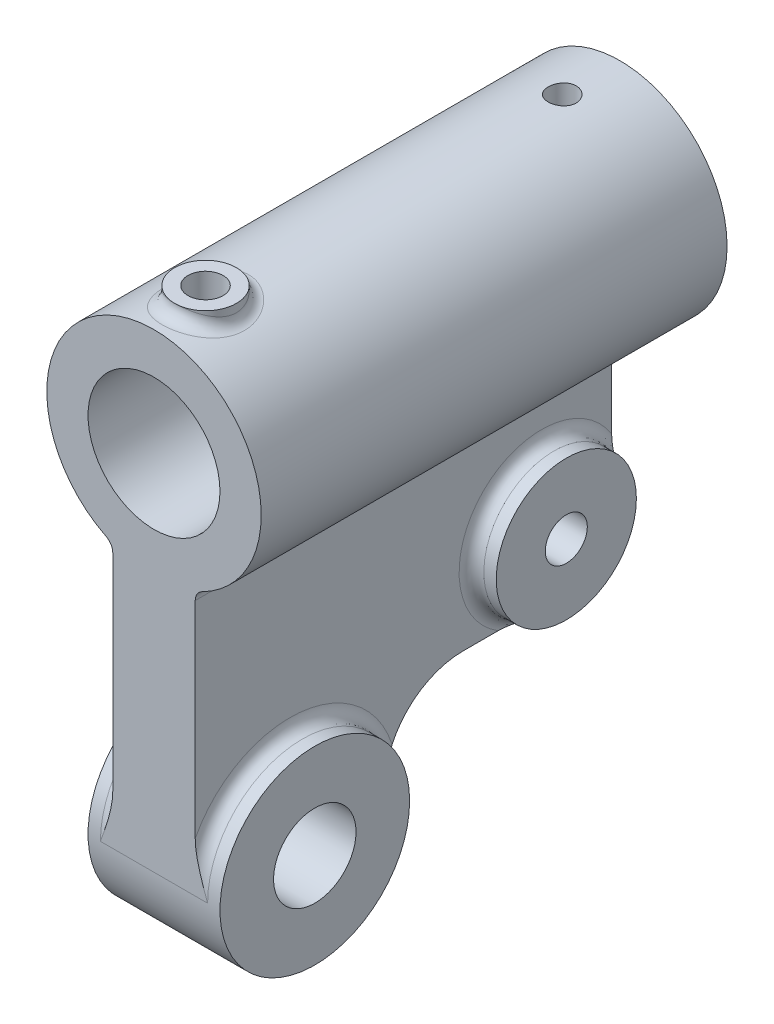
SolidWorks part; units mm, degrees
ref_plane "前基準面" through (0, 0, 0) normal (0, 0, 1) x (1, 0, 0)
ref_plane "上基準面" through (0, 0, 0) normal (0, 1, 0) x (1, 0, 0)
ref_plane "右基準面" through (0, 0, 0) normal (1, 0, 0) x (0, 0, -1)
sketch "草圖1" plane through (0, 0, 0) normal (0, 0, 1) x (1, 0, 0)
  circle A0 centre (0, 0) radius 26
  circle A1 centre (0, 0) radius 16
  dimension "D1" = 52
  dimension "D2" = 32
extrude "伸長1" add sketch "草圖1" against normal blind 113
sketch "草圖2" plane through (0, 0, 0) normal (1, 0, 0) x (0, 0, -1)
  line L0 (12.5, 12.9939) -> (12.5, 38.1989) construction
  line L1 (12.5, 29) -> (5, 29)
  line L2 (5, 29) -> (5, 21.929)
  line L3 (5, 21.929) -> (12.5, 21.929)
  line L4 (0, 26) -> (0, -26) construction
  line L5 (113, 26) -> (0, 26) construction
  line L6 (12.5, 29) -> (12.5, 21.929)
  dimension "D1" = 12.5
  dimension "D2" = 15
  dimension "D3" = 3
revolve "旋轉1" add sketch "草圖2" angle 360 about L0
sketch "草圖4" plane through (0, 0, 0) normal (1, 0, 0) x (0, 0, -1)
  line L0 (0, -16.5) -> (0, -88)
  line L1 (0, 26) -> (0, -26) construction
  line L2 (65, -69) -> (84, -69)
  line L3 (101, -52) -> (101, -16.5)
  line L7 (101, -16.5) -> (0, -16.5)
  line L8 (0, -16) -> (113, -16) construction
  arc A0 (0, -88) -> (46, -88) centre (23, -88) ccw
  arc A1 (46, -88) -> (65, -69) centre (65, -88) cw
  arc A2 (84, -69) -> (101, -52) centre (84, -52) ccw
  circle A4 centre (23, -88) radius 10
  dimension "D1" = 23
  dimension "D2" = 20
  dimension "D3" = 88
  dimension "D4" = 36
  dimension "D5" = 17
  dimension "D6" = 61
  dimension "D8" = 0.5
extrude "伸長2" add sketch "草圖4" along normal mid plane 20 contours L0 A0 A1 L2 A2 L3 A4 region at (0, -52.2468, -44.3643)
sketch "草圖5" plane through (0, 0, 0) normal (1, 0, 0) x (0, 0, -1)
  circle A0 centre (23, -88) radius 23
  arc A1 (0, -88) -> (46, -88) centre (23, -88) ccw construction
  circle A2 centre (23, -88) radius 10 construction
  circle A3 centre (23, -88) radius 10
extrude "伸長3" add sketch "草圖5" along normal mid plane 32
sketch "草圖6" plane through (10, 0, 0) normal (1, 0, 0) x (0, 0, -1)
  circle A0 centre (84, -52) radius 17
  arc A1 (84, -69) -> (101, -52) centre (84, -52) ccw construction
extrude "伸長4" add sketch "草圖6" along normal blind 6
fillet "圓角1" radius 3 1 edges at (0, -26, -101)
fillet "圓角2" radius 3 6 edges at (-1.3841, 25.9631, -5.1288) (-10, -65, -23) (10, -65, -23) (10, -39.9792, -71.9792) (-10, -24, -52) (10, -24, -52)
hole_wizard "M10 螺紋孔1" positions "草圖8" profile "草圖7" tap size "M10" standard "ISO" end condition up to next
sketch "草圖8" plane through (0, 29, 0) normal (0, 1, 0) x (-1, 0, 0)
  point P0 (0, -12.5)
sketch "草圖7" plane through (0, 29, -12.5) normal (1, 0, 0) x (0, 0, 1)
  line L0 (0, 0) -> (0, 13)
  line L1 (0, 13) -> (4.25, 13)
  line L2 (4.25, 13) -> (4.25, 0)
  line L5 (4.25, 0) -> (0, 0)
  line L11 (0, -6.35) -> (0, 107.95) construction
  dimension "貫穿螺孔鑽直徑" = 8.5
  dimension "貫穿螺孔鑽深度" = 13
cosmetic thread "鑽孔螺紋1" parameters "D2"=10
hole_wizard "M8 螺紋孔1" positions "3D草圖1" profile "草圖13" tap size "M8" standard "ISO" end condition up to next
sketch3d "3D草圖1"
  point P0 (0, 26, -99)
  dimension "D1" = 14
sketch "草圖13" plane through (0, 26, -99) normal (1, 0, 0) x (0, 0, 1)
  line L0 (0, 0) -> (0, 10)
  line L1 (0, 10) -> (3.4, 10)
  line L2 (3.4, 10) -> (3.4, 0)
  line L5 (3.4, 0) -> (0, 0)
  line L11 (0, -6.35) -> (0, 107.95) construction
  dimension "貫穿螺孔鑽直徑" = 6.8
  dimension "貫穿螺孔鑽深度" = 10
cosmetic thread "鑽孔螺紋4" parameters "D2"=8
hole_wizard "M12 螺紋孔1" positions "草圖12" profile "草圖11" tap size "M12" standard "ISO" end condition up to next
sketch "草圖12" plane through (16, 0, 0) normal (1, 0, 0) x (0, 0, -1)
  point P0 (84, -52)
sketch "草圖11" plane through (16, -52, -84) normal (0, 1, 0) x (0, 0, -1)
  line L0 (0, 0) -> (0, 26)
  line L1 (0, 26) -> (5.1, 26)
  line L2 (5.1, 26) -> (5.1, 0)
  line L5 (5.1, 0) -> (0, 0)
  line L11 (0, -6.35) -> (0, 107.95) construction
  dimension "貫穿螺孔鑽直徑" = 10.2
  dimension "貫穿螺孔鑽深度" = 26
cosmetic thread "鑽孔螺紋3" parameters "D2"=12
